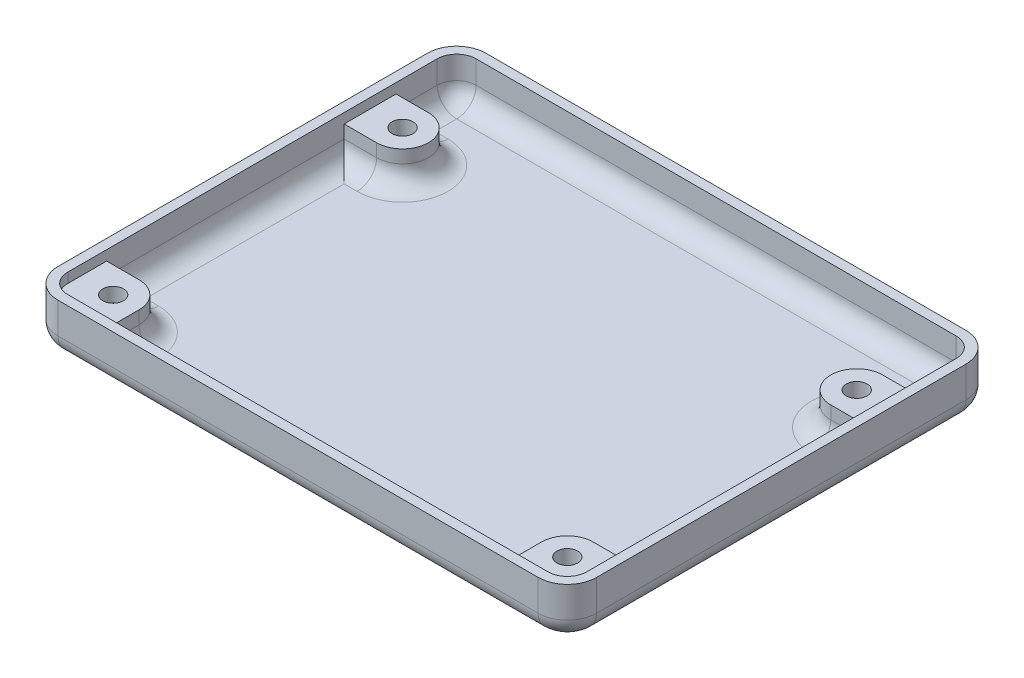
SolidWorks part; units mm, degrees
ref_plane "Front Plane" through (0, 0, 0) normal (0, 0, 1) x (1, 0, 0)
ref_plane "Top Plane" through (0, 0, 0) normal (0, 1, 0) x (1, 0, 0)
ref_plane "Right Plane" through (0, 0, 0) normal (1, 0, 0) x (0, 0, -1)
sketch "Sketch1" plane through (0, 0, 0) normal (0, 1, 0) x (1, 0, 0)
  line L0 (0, 4.1695) -> (0, 0) construction
  line L1 (-37, -27.3) -> (37, -27.3)
  line L2 (-40, -24.3) -> (-40, 32.6391)
  line L3 (-37, 35.6391) -> (37, 35.6391)
  line L4 (40, -24.3) -> (40, 32.6391)
  line L5 (-40, -27.3) -> (40, 35.6391) construction
  line L6 (-40, 35.6391) -> (40, -27.3) construction
  line L7 (-37, 37.1391) -> (37, 37.1391)
  line L8 (41.5, -24.3) -> (41.5, 32.6391)
  line L9 (-37, -28.8) -> (37, -28.8)
  line L10 (-41.5, -24.3) -> (-41.5, 32.6391)
  line L11 (-7.5915, 37.1391) -> (5.6585, 37.1391) construction
  line L12 (-38, -25.3) -> (38, -25.3) construction
  line L13 (-38, 25.3) -> (-38, -25.3) construction
  arc A0 (37, 35.6391) -> (40, 32.6391) centre (37, 32.6391) cw
  arc A1 (37, -27.3) -> (40, -24.3) centre (37, -24.3) ccw
  arc A2 (-37, -27.3) -> (-40, -24.3) centre (-37, -24.3) cw
  arc A3 (-40, 32.6391) -> (-37, 35.6391) centre (-37, 32.6391) cw
  arc A4 (37, 37.1391) -> (41.5, 32.6391) centre (37, 32.6391) cw
  arc A5 (37, -28.8) -> (41.5, -24.3) centre (37, -24.3) ccw
  arc A6 (-37, -28.8) -> (-41.5, -24.3) centre (-37, -24.3) cw
  arc A7 (-41.5, 32.6391) -> (-37, 37.1391) centre (-37, 32.6391) cw
  point P0 (0, 4.1695)
  dimension "D1" = 3
  dimension "D3" = 2
  dimension "D4" = 2
  dimension "D2" = 1.5
extrude "Boss-Extrude1" add sketch "Sketch1" along normal up to surface (7.78 mm away)
extrude "Boss-Extrude2" add sketch "Sketch1<2>" along normal blind 1.25 contours A3 L2 A2 L1 A1 L4 A0 L3 region at (0, 0, -4.1695)
sketch "Sketch1<2>" plane through (0, 0, 0) normal (0, 1, 0) x (1, 0, 0) same geometry as "Sketch1"
sketch "Sketch2" plane through (0, 1.25, 0) normal (0, 1, 0) x (1, 0, 0)
  line L0 (-40, 26.3) -> (-35, 26.3)
  line L1 (-35, -22.3) -> (35, -22.3) construction
  line L2 (-35, -22.3) -> (-35, 22.3) construction
  line L3 (-35, 22.3) -> (35, 22.3) construction
  line L4 (35, -22.3) -> (35, 22.3) construction
  line L5 (-35, -22.3) -> (35, 22.3) construction
  line L6 (-35, 22.3) -> (35, -22.3) construction
  line L7 (-40, 26.3) -> (-40, 18.3)
  line L8 (-40, 18.3) -> (-35, 18.3)
  line L9 (-40, -24.3) -> (-40, 32.6391) construction
  line L10 (35, 26.3) -> (40, 26.3)
  line L11 (40, -24.3) -> (40, 32.6391) construction
  line L12 (40, 26.3) -> (40, 18.3)
  line L13 (40, 18.3) -> (35, 18.3)
  line L14 (-40, -24.3) -> (-40, -18.3)
  line L15 (-40, -18.3) -> (-35, -18.3)
  line L16 (-31, -22.3) -> (-31, -27.3)
  line L17 (-37, -27.3) -> (37, -27.3) construction
  line L18 (-31, -27.3) -> (-37, -27.3)
  line L19 (35, -18.3) -> (40, -18.3)
  line L20 (40, -18.3) -> (40, -24.3)
  line L21 (37, -27.3) -> (31, -27.3)
  line L22 (31, -27.3) -> (31, -22.3)
  circle A0 centre (-35, 22.3) radius 1.6
  circle A1 centre (-35, -22.3) radius 1.6
  circle A2 centre (35, -22.3) radius 1.6
  circle A3 centre (35, 22.3) radius 1.6
  circle A4 centre (35, 22.3) radius 1.5 construction
  arc A5 (-35, 26.3) -> (-35, 18.3) centre (-35, 22.3) cw
  arc A6 (35, 18.3) -> (35, 26.3) centre (35, 22.3) cw
  arc A7 (-35, -18.3) -> (-31, -22.3) centre (-35, -22.3) cw
  arc A8 (-37, -27.3) -> (-40, -24.3) centre (-37, -24.3) cw
  arc A9 (40, -24.3) -> (37, -27.3) centre (37, -24.3) cw
  arc A10 (31, -22.3) -> (35, -18.3) centre (35, -22.3) cw
  point P8 (0, 0)
  point P44 (37, -27.3)
  dimension "D1" = 3.2
  dimension "D2" = 8
extrude "Boss-Extrude3" add sketch "Sketch2" along normal up to surface (5 mm away) up to face at (0, 0, -4.1695)
fillet "Fillet1" radius 3 28 edges at (-40.182, 0, 27.482) (-41.5, 0, -4.1695) (-40.182, 0, -35.821) (0, 0, -37.1391) (40.182, 0, -35.821) (41.5, 0, -4.1695) (40.182, 0, 27.482) (-31, 1.25, 24.8) (-32.1716, 1.25, 19.4716) (-37.5, 1.25, 18.3) (-40, 1.25, 0) (-37.5, 1.25, -18.3) (-31, 1.25, -22.3) (-37.5, 1.25, -26.3) (-40, 1.25, -29.4695) (-39.1213, 1.25, -34.7604) (0, 1.25, -35.6391) (39.1213, 1.25, -34.7604) (40, 1.25, -29.4695) (37.5, 1.25, -26.3) (31, 1.25, -22.3) (37.5, 1.25, -18.3) (40, 1.25, 0) (37.5, 1.25, 18.3) (32.1716, 1.25, 19.4716) (31, 1.25, 24.8) (0, 1.25, 27.3) (0, 0, 28.8)
sketch "Sketch3" plane through (0, 0, 0) normal (0, -1, 0) x (1, 0, 0)
  line L1 (35, -22.3) -> (-35, -22.3) construction
  line L2 (35, -22.3) -> (35, 22.3) construction
  line L3 (35, 22.3) -> (-35, 22.3) construction
  line L4 (-35, -22.3) -> (-35, 22.3) construction
  circle A0 centre (35, -22.3) radius 2.75
  circle A1 centre (35, 22.3) radius 2.75
  circle A2 centre (-35, -22.3) radius 2.75
  circle A3 centre (-35, 22.3) radius 2.75
  circle A4 centre (-35, -22.3) radius 1.6 construction
  circle A5 centre (35, 22.3) radius 1.6 construction
  point P13 (-35, -21.9924)
  dimension "D1" = 5.5
extrude "Cut-Extrude1" cut sketch "Sketch3" against normal blind 4
